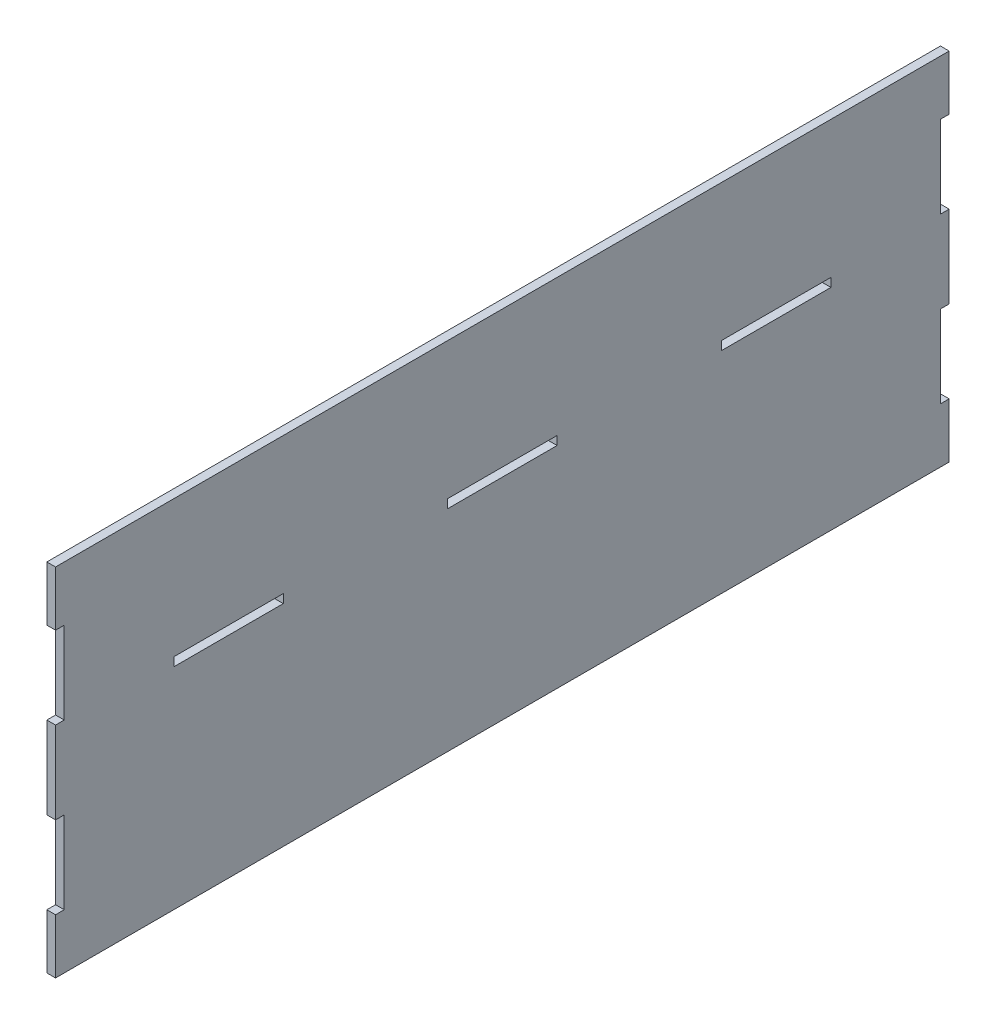
SolidWorks part; units mm, degrees
ref_plane "前视" through (0, 0, 0) normal (0, 0, 1) x (1, 0, 0)
ref_plane "上视" through (0, 0, 0) normal (0, 1, 0) x (1, 0, 0)
ref_plane "右视" through (0, 0, 0) normal (1, 0, 0) x (0, 0, -1)
sketch "Sketch1" plane through (0, 0, 0) normal (1, 0, 0) x (0, 0, -1)
  line L1 (0, 0) -> (326.35, 0)
  line L2 (0, 0) -> (0, -130)
  line L3 (0, -130) -> (326.35, -130)
  line L4 (326.35, 0) -> (326.35, -130)
  dimension "D1" = 326.35
  dimension "D2" = 130
extrude "Boss-Extrude1" add sketch "Sketch1" along normal blind 3.175
ref_axis "Axis1" through (3.175, 0, -163.175) along (0, 1, 0)
sketch "Sketch2" plane through (3.175, 0, 0) normal (1, 0, 0) x (0, 0, -1)
  line L0 (0, -130) -> (326.35, -130) construction
  line L1 (43.175, -50) -> (83.175, -50)
  line L2 (43.175, -50) -> (43.175, -53.175)
  line L3 (43.175, -53.175) -> (83.175, -53.175)
  line L4 (83.175, -50) -> (83.175, -53.175)
  line L5 (0, 0) -> (0, -130) construction
  line L6 (326.35, -130) -> (326.35, 0) construction
  line L7 (143.175, -50) -> (183.175, -50)
  line L8 (143.175, -50) -> (143.175, -53.175)
  line L9 (143.175, -53.175) -> (183.175, -53.175)
  line L10 (183.175, -50) -> (183.175, -53.175)
  line L11 (243.175, -50) -> (283.175, -50)
  line L12 (243.175, -50) -> (243.175, -53.175)
  line L13 (243.175, -53.175) -> (283.175, -53.175)
  line L14 (283.175, -50) -> (283.175, -53.175)
  line L15 (326.35, -20) -> (323.175, -20)
  line L16 (326.35, -20) -> (326.35, -50)
  line L17 (326.35, -50) -> (323.175, -50)
  line L18 (323.175, -20) -> (323.175, -50)
  line L19 (326.35, 0) -> (0, 0) construction
  line L21 (326.35, -80) -> (323.175, -80)
  line L22 (326.35, -80) -> (326.35, -110)
  line L23 (326.35, -110) -> (323.175, -110)
  line L24 (323.175, -80) -> (323.175, -110)
  line L25 (0, -20) -> (3.175, -20)
  line L26 (0, -20) -> (0, -50)
  line L27 (0, -50) -> (3.175, -50)
  line L28 (3.175, -20) -> (3.175, -50)
  line L29 (0, -80) -> (3.175, -80)
  line L30 (0, -80) -> (0, -110)
  line L31 (0, -110) -> (3.175, -110)
  line L32 (3.175, -80) -> (3.175, -110)
  dimension "D1" = 80
  dimension "D2" = 3.175
  dimension "D3" = 43.175
  dimension "D4" = 40
  dimension "D5" = 60
  dimension "D6" = 40
  dimension "D7" = 40
  dimension "D8" = 60
  dimension "D9" = 20
  dimension "D10" = 3.175
  dimension "D11" = 30
  dimension "D12" = 30
  dimension "D13" = 30
  dimension "D14" = 20
  dimension "D15" = 30
  dimension "D16" = 3.175
  dimension "D17" = 30
  dimension "D18" = 30
  dimension "D19" = 3.175
extrude "Cut-Extrude1" cut sketch "Sketch2" against normal blind 10
